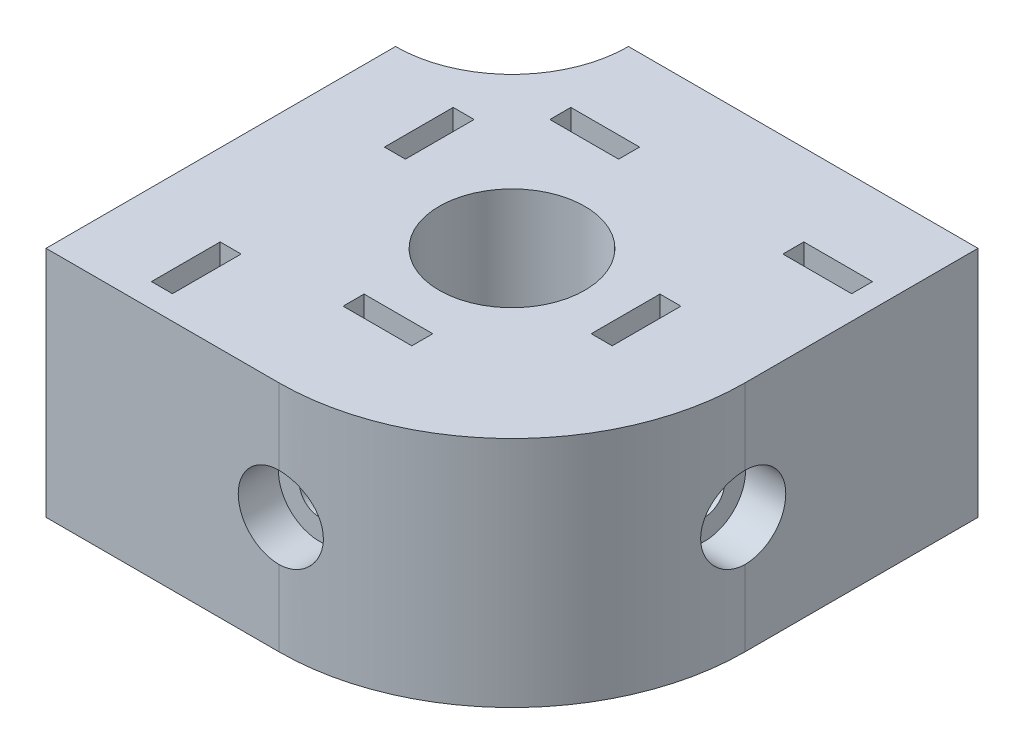
SolidWorks part; units mm, degrees
ref_plane "Front Plane" through (0, 0, 0) normal (0, 0, 1) x (1, 0, 0)
ref_plane "Top Plane" through (0, 0, 0) normal (0, 1, 0) x (1, 0, 0)
ref_plane "Right Plane" through (0, 0, 0) normal (1, 0, 0) x (0, 0, -1)
sketch "Sketch1" plane through (0, 0, 0) normal (0, 1, 0) x (1, 0, 0)
  line L1 (-20, -20) -> (20, -20)
  line L2 (-20, -20) -> (-20, 20)
  line L3 (-20, 20) -> (20, 20)
  line L4 (20, -20) -> (20, 20)
  line L5 (-20, -20) -> (20, 20) construction
  line L6 (-20, 20) -> (20, -20) construction
  circle A0 centre (0, 0) radius 6.25
  point P0 (0, 0)
  dimension "D2" = 12.5
  dimension "D1" = 40
extrude "Boss-Extrude1" add sketch "Sketch1" along normal blind 20
sketch "Sketch2" plane through (-20, 0, 0) normal (-1, 0, 0) x (0, 0, 1)
  line L0 (-5, 15) -> (0, 5) construction
  line L1 (0, 5) -> (15, 15) construction
  line L2 (15, 15) -> (-5, 15) construction
  line L3 (-20, 20) -> (20, 20) construction
  line L4 (-20, 0) -> (20, 0) construction
  line L5 (20, 20) -> (20, 0) construction
  line L6 (-20, 20) -> (-20, 0) construction
  line L7 (0, -11) -> (0, 11) construction
  circle A0 centre (-5, 15) radius 1.7
  circle A1 centre (15, 15) radius 1.7
  circle A2 centre (0, 5) radius 1.7
  dimension "D5" = 3.4
  dimension "D1" = 5
  dimension "D2" = 5
  dimension "D3" = 5
  dimension "D4" = 15
extrude "Cut-Extrude1" cut sketch "Sketch2" against normal blind 11
sketch "Sketch3" plane through (-20, 0, 0) normal (-1, 0, 0) x (0, 0, 1)
  line L1 (-7.95, 12.05) -> (-2.05, 12.05)
  line L2 (-7.95, 12.05) -> (-7.95, 17.95)
  line L3 (-7.95, 17.95) -> (-2.05, 17.95) construction
  line L4 (-2.05, 12.05) -> (-2.05, 17.95)
  line L5 (-7.95, 12.05) -> (-2.05, 17.95) construction
  line L6 (-7.95, 17.95) -> (-2.05, 12.05) construction
  line L7 (12.05, 12.05) -> (17.95, 12.05)
  line L8 (12.05, 12.05) -> (12.05, 17.95)
  line L9 (12.05, 17.95) -> (17.95, 17.95) construction
  line L10 (17.95, 12.05) -> (17.95, 17.95)
  line L11 (12.05, 12.05) -> (17.95, 17.95) construction
  line L12 (12.05, 17.95) -> (17.95, 12.05) construction
  line L13 (-2.95, 7.95) -> (2.95, 7.95)
  line L14 (-2.95, 7.95) -> (-2.95, 2.05)
  line L15 (-2.95, 2.05) -> (2.95, 2.05) construction
  line L16 (2.95, 7.95) -> (2.95, 2.05)
  line L17 (-2.95, 7.95) -> (2.95, 2.05) construction
  line L18 (-2.95, 2.05) -> (2.95, 7.95) construction
  line L20 (-7.95, 17.95) -> (-7.95, 20)
  line L21 (-20, 20) -> (20, 20) construction
  line L22 (-7.95, 20) -> (-2.05, 20)
  line L23 (-2.05, 20) -> (-2.05, 17.95)
  line L24 (12.05, 17.95) -> (12.05, 20)
  line L25 (12.05, 20) -> (17.95, 20)
  line L26 (17.95, 20) -> (17.95, 17.95)
  line L27 (-2.95, 2.05) -> (-2.95, 0)
  line L28 (-20, 0) -> (20, 0) construction
  line L29 (-2.95, 0) -> (2.95, 0)
  line L30 (2.95, 0) -> (2.95, 2.05)
  point P0 (-5, 15)
  point P6 (15, 15)
  point P12 (0, 5)
  dimension "D1" = 5.9
  dimension "D2" = 5.9
extrude "Cut-Extrude2" cut sketch "Sketch3" against normal blind 1.8 from offset 7 offset against normal yes
sketch "Sketch4" plane through (0, 0, 20) normal (0, 0, 1) x (1, 0, 0)
  line L0 (0, 0) -> (0, 20) construction
  line L1 (-20, 20) -> (20, 20) construction
  circle A0 centre (0, 10) radius 1.7
  dimension "D1" = 3.4
extrude "Cut-Extrude3" cut sketch "Sketch4" against normal up to next
sketch "Sketch5" plane through (0, 0, 20) normal (0, 0, 1) x (1, 0, 0)
  line L0 (-2.95, 12.95) -> (-2.95, 20)
  line L1 (-2.95, 7.05) -> (2.95, 7.05)
  line L2 (-2.95, 7.05) -> (-2.95, 12.95)
  line L3 (-2.95, 12.95) -> (2.95, 12.95) construction
  line L4 (2.95, 7.05) -> (2.95, 12.95)
  line L5 (-2.95, 7.05) -> (2.95, 12.95) construction
  line L6 (-2.95, 12.95) -> (2.95, 7.05) construction
  line L7 (-20, 20) -> (20, 20) construction
  line L8 (-2.95, 20) -> (2.95, 20)
  line L9 (2.95, 20) -> (2.95, 12.95)
  point P0 (0, 10)
  dimension "D1" = 5.9
extrude "Cut-Extrude4" cut sketch "Sketch5" against normal blind 1.8 from offset 8.45 offset against normal yes
sketch "Sketch6" plane through (0, 0, 20) normal (0, 0, 1) x (1, 0, 0)
  circle A0 centre (0, 10) radius 3.5
  dimension "D1" = 7
extrude "Cut-Extrude5" cut sketch "Sketch6" against normal blind 3.45
ref_plane "Plane1" through (0, 0, 0) normal (-0.7071, 0, 0.7071) x (0.7071, 0, 0.7071)
mirror "Mirror1" about plane through (0, 0, 0) normal (-0.7071, 0, 0.7071) of "Cut-Extrude5", "Cut-Extrude4", "Cut-Extrude3", "Cut-Extrude2", "Cut-Extrude1"
fillet "Fillet1" radius 20 1 edges at (20, 10, 20)
sketch "Sketch7" plane through (0, 20, 0) normal (0, 1, 0) x (1, 0, 0)
  line L0 (20, 20) -> (-20, 20) construction
  line L1 (-20, 20) -> (-20, -20) construction
  line L2 (-20, 10) -> (-20, 20)
  line L3 (-20, 20) -> (-10, 20)
  arc A0 (-10, 20) -> (-20, 10) centre (-20, 20) cw
  dimension "D1" = 10
extrude "Cut-Extrude6" cut sketch "Sketch7" against normal through all
equation "\"M3_d\"= 3.4"
equation "\"D5@Sketch2\"= \"M3_d\""
equation "\"M3_nut_s\"= 5.9"
equation "\"M3_nut_m\"= 1.8"
equation "\"D1@Sketch3\"=\"M3_nut_s\""
equation "\"D2@Sketch3\"=\"M3_nut_s\" "
equation "\"D1@Cut-Extrude2\"=\"M3_nut_m\""
equation "\"D1@Sketch4\"=\"M3_d\""
equation "\"D1@Sketch5\"=\"M3_nut_s\""
equation "\"D1@Cut-Extrude4\"=\"M3_nut_m\""
